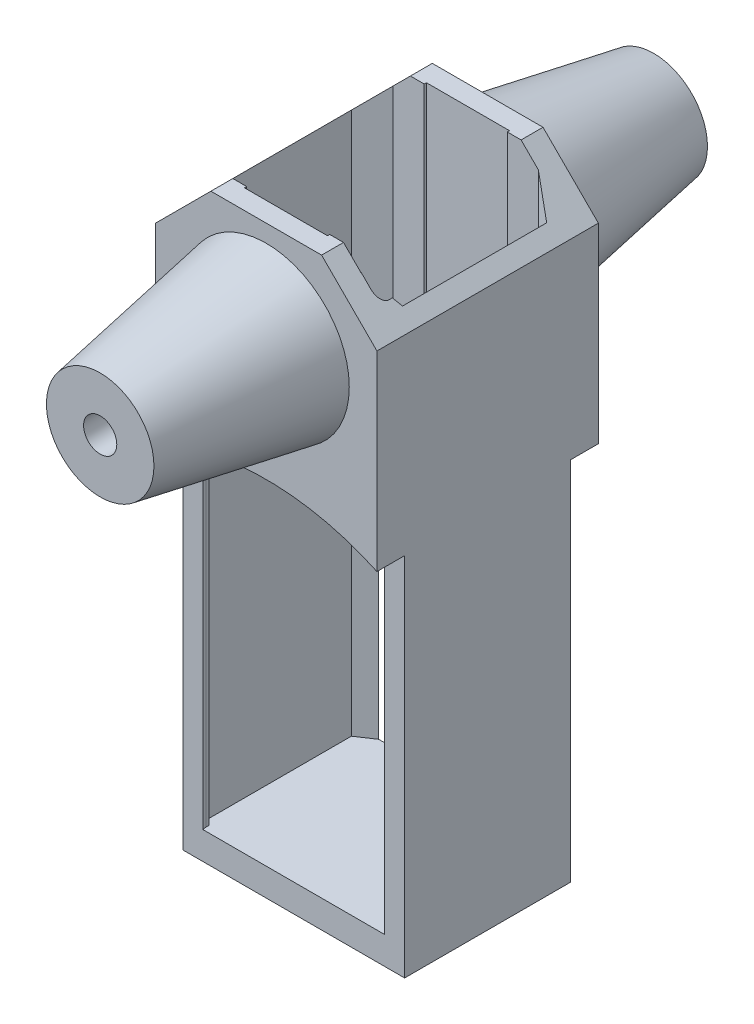
SolidWorks part; units mm, degrees
ref_plane "Front Plane" through (0, 0, 0) normal (0, 0, 1) x (1, 0, 0)
ref_plane "Top Plane" through (0, 0, 0) normal (0, 1, 0) x (1, 0, 0)
ref_plane "Right Plane" through (0, 0, 0) normal (1, 0, 0) x (0, 0, -1)
sketch "Sketch1" plane through (0, 0, 0) normal (0, 1, 0) x (1, 0, 0)
  line L0 (4.7625, -10.1854) -> (8.3298, -10.1854)
  line L5 (-4.7625, 10.1854) -> (-4.7625, 10.4394)
  line L6 (-12.7, -12.7) -> (12.7, -12.7)
  line L7 (4.7625, 10.1854) -> (8.3298, 10.1854)
  line L8 (-8.3298, 10.1854) -> (-11.2014, 8.271)
  line L9 (-8, 10.1) -> (-11, 8.1) construction
  line L10 (0, 0) -> (-11.2014, 0) construction
  line L11 (0, 0) -> (0, 10.4394) construction
  line L12 (-8.3298, -10.1854) -> (-8.3769, -10.154)
  line L13 (8.3298, -10.1854) -> (8.3769, -10.154)
  line L14 (8.3298, 10.1854) -> (11.2014, 8.271)
  line L15 (-8.3298, 10.1854) -> (-4.7625, 10.1854)
  line L16 (-12.7, 12.7) -> (-12.7, -12.7)
  line L17 (12.7, 12.7) -> (12.7, -12.7)
  line L34 (-10.504, -8.7359) -> (-11.2014, -8.271)
  line L35 (8.3769, -10.154) -> (9.4165, -10.154)
  line L36 (9.5863, -10.1409) -> (9.6154, -10.1409)
  line L37 (-9.5863, -10.1409) -> (-9.6154, -10.1409)
  line L38 (-8.75, -10.154) -> (-9.4165, -10.154)
  line L39 (-10.504, -9.1) -> (-10.504, -8.9)
  line L40 (-9.5863, -10.1409) -> (-9.6154, -10.1409)
  line L41 (-8.3769, -10.154) -> (-9.4165, -10.154)
  line L42 (-10.504, -9.1) -> (-10.504, -8.7359)
  line L43 (10.504, -9.1) -> (10.504, -8.7359)
  line L44 (10.504, -8.7359) -> (11.2014, -8.271)
  line L284 (-12.7, 12.7) -> (12.7, 12.7)
  line L286 (-12.7, -12.7) -> (12.7, 12.7) construction
  line L287 (-12.7, 12.7) -> (12.7, -12.7) construction
  line L288 (-8.3298, -10.1854) -> (-4.7625, -10.1854)
  line L289 (-11.2014, -8.271) -> (-11.2014, 8.271)
  line L291 (11.2014, -8.271) -> (11.2014, 8.271)
  line L326 (-4.7625, 10.4394) -> (4.7625, 10.4394)
  line L327 (4.7625, 10.4394) -> (4.7625, 10.1854)
  line L328 (-4.7625, -10.1854) -> (-4.7625, -10.4394)
  line L335 (-4.7625, -10.4394) -> (4.7625, -10.4394)
  line L338 (4.7625, -10.4394) -> (4.7625, -10.1854)
  arc A7 (9.5863, -10.1409) -> (9.4165, -10.154) centre (9.4168, -9.0458) cw
  arc A8 (-9.5863, -10.1409) -> (-9.4165, -10.154) centre (-9.4168, -9.0458) ccw
  arc A9 (-10.504, -9.1) -> (-9.6154, -10.1409) centre (-9.45, -9.1) ccw
  arc A10 (-9.5863, -10.1409) -> (-9.4165, -10.154) centre (-9.4168, -9.0458) ccw
  arc A11 (-10.504, -9.1) -> (-9.6154, -10.1409) centre (-9.45, -9.1) ccw
  arc A12 (10.504, -9.1) -> (9.6154, -10.1409) centre (9.45, -9.1) cw
  point P0 (0, 0)
  point P6 (0, 0)
  point P15 (0, 10.4394)
  point P23 (0, -10.4394)
  dimension "D1" = 25.4
  dimension "D2" = 25.4
  dimension "D3" = 0.254
  dimension "D5" = 9.525
  dimension "D6" = 22.4028
  dimension "D7" = 0.254
  dimension "D8" = 20.3708
  dimension "D9" = 0.254
  dimension "D15" = 0.254
extrude "Boss-Extrude1" add sketch "Sketch1" along normal blind 67.056
sketch "Sketch4" plane through (0, 0, 0) normal (0, -1, 0) x (-1, 0, 0)
  line L1 (12.7, -12.7) -> (-12.7, -12.7)
  line L2 (12.7, -12.7) -> (12.7, 12.7)
  line L3 (12.7, 12.7) -> (-12.7, 12.7)
  line L4 (-12.7, -12.7) -> (-12.7, 12.7)
extrude "Boss-Extrude4" add sketch "Sketch4" along normal blind 3.175
sketch "Sketch5" plane through (0, 0, -12.7) normal (0, 0, -1) x (-1, 0, 0)
  circle A0 centre (0, 11.43) radius 30.1625
  dimension "D2" = 60.325
  dimension "D1" = 11.43
extrude "Cut-Extrude1" cut sketch "Sketch5" against normal blind 3.175
mirror "Mirror1" about plane through (0, 0, 0) normal (0, 0, 1) of "Cut-Extrude1"
sketch "Sketch7" plane through (0, 0, 12.7) normal (0, 0, 1) x (1, 0, 0)
  circle A0 centre (0, 55.5371) radius 9.525
  circle A1 centre (0, 11.0871) radius 4.7625 construction
  dimension "D2" = 19.05
  dimension "D1" = 44.45
extrude "Boss-Extrude6" add sketch "Sketch7" along normal blind 19.05 draft 10
sketch "Sketch8" plane through (0, 0, 31.75) normal (0, 0, 1) x (1, 0, 0)
  circle A0 centre (0, 55.5371) radius 1.905
  dimension "D1" = 3.81
extrude "Cut-Extrude2" cut sketch "Sketch8" against normal blind 12.7
mirror "Mirror3" about plane through (0, 0, 0) normal (0, 0, 1) of "Cut-Extrude2", "Boss-Extrude6"
chamfer "Chamfer1" distance 6.35 angle 45 2 edges at (12.7, 67.056, 0) (-12.7, 67.056, 0)
